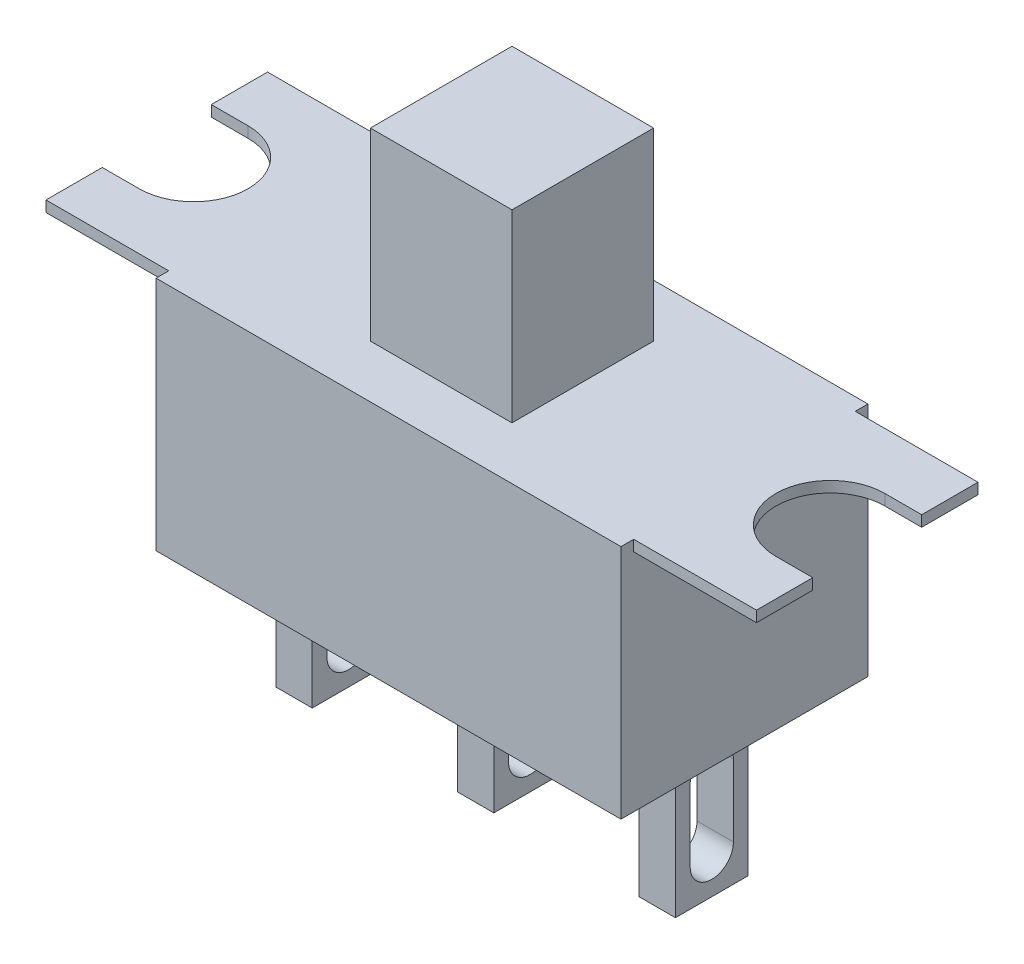
SolidWorks part; units mm, degrees
ref_plane "Front" through (0, 0, 0) normal (0, 0, 1) x (1, 0, 0)
ref_plane "Top" through (0, 0, 0) normal (0, 1, 0) x (1, 0, 0)
ref_plane "Side" through (0, 0, 0) normal (1, 0, 0) x (0, 0, -1)
ref_axis "X_Axis" through (-20.1896, 0, 0) along (1, 0, 0)
ref_axis "Y_Axis" through (0, -14.8261, 0) along (0, 1, 0)
ref_axis "Z_Axis" through (0, 0, -19.842) along (0, 0, 1)
sketch "Sketch1" plane through (0, 0, 0) normal (0, 1, 0) x (1, 0, 0)
  line L1 (6.4, 3.4) -> (-6.4, 3.4)
  line L2 (6.4, 3.4) -> (6.4, -3.4)
  line L3 (6.4, -3.4) -> (-6.4, -3.4)
  line L4 (-6.4, 3.4) -> (-6.4, -3.4)
  line L5 (6.4, 3.4) -> (-6.4, -3.4) construction
  line L6 (6.4, -3.4) -> (-6.4, 3.4) construction
  point P0 (0, 0)
  dimension "D1" = 6.8
  dimension "D2" = 12.8
extrude "Boss-Extrude1" add sketch "Sketch1" along normal blind 6.5
sketch "Sketch2" plane through (0, 6.5, 0) normal (0, 1, 0) x (1, 0, 0)
  line L0 (0, 3.05) -> (0, -3.05) construction
  line L1 (9.78, 3.05) -> (-9.78, 3.05)
  line L2 (9.78, 3.05) -> (9.78, 1.5)
  line L3 (9.78, -3.05) -> (-9.78, -3.05)
  line L4 (-9.78, 3.05) -> (-9.78, 1.5)
  line L5 (9.78, 3.05) -> (-9.78, -3.05) construction
  line L6 (9.78, -3.05) -> (-9.78, 3.05) construction
  line L7 (-8.765, 1.5) -> (-9.78, 1.5)
  line L9 (-9.78, -1.5) -> (-8.765, -1.5)
  line L10 (8.765, 1.5) -> (9.78, 1.5)
  line L12 (9.78, -1.5) -> (8.765, -1.5)
  line L13 (-9.78, -1.5) -> (-9.78, -3.05)
  line L14 (9.78, -1.5) -> (9.78, -3.05)
  arc A0 (-8.765, -1.5) -> (-8.765, 1.5) centre (-8.765, 0) ccw
  arc A1 (8.765, 1.5) -> (8.765, -1.5) centre (8.765, 0) ccw
  point P0 (0, 0)
  dimension "D3" = 3
  dimension "D1" = 6.1
  dimension "D2" = 19.56
  dimension "D4" = 17.53
extrude "Boss-Extrude2" add sketch "Sketch2" against normal blind 0.3
sketch "Sketch3" plane through (0, 6.5, 0) normal (0, 1, 0) x (1, 0, 0)
  line L1 (1.95, 1.95) -> (-1.95, 1.95)
  line L2 (1.95, 1.95) -> (1.95, -1.95)
  line L3 (1.95, -1.95) -> (-1.95, -1.95)
  line L4 (-1.95, 1.95) -> (-1.95, -1.95)
  line L5 (1.95, 1.95) -> (-1.95, -1.95) construction
  line L6 (1.95, -1.95) -> (-1.95, 1.95) construction
  point P0 (0, 0)
  dimension "D1" = 3.9
  dimension "D2" = 3.9
extrude "Boss-Extrude3" add sketch "Sketch3" along normal blind 5.08
sketch "Sketch4" plane through (0, 0, 0) normal (0, -1, 0) x (1, 0, 0)
  line L0 (-6.4, 0) -> (6.4, 0) construction
  line L1 (-0.5, 1) -> (0.5, 1)
  line L2 (-0.5, 1) -> (-0.5, -1)
  line L3 (-0.5, -1) -> (0.5, -1)
  line L4 (0.5, 1) -> (0.5, -1)
  line L5 (-0.5, 1) -> (0.5, -1) construction
  line L6 (-0.5, -1) -> (0.5, 1) construction
  line L7 (4.5, 1) -> (5.5, 1)
  line L8 (4.5, 1) -> (4.5, -1)
  line L9 (4.5, -1) -> (5.5, -1)
  line L10 (5.5, 1) -> (5.5, -1)
  line L11 (4.5, 1) -> (5.5, -1) construction
  line L12 (4.5, -1) -> (5.5, 1) construction
  line L13 (-5.5, 1) -> (-4.5, 1)
  line L14 (-5.5, 1) -> (-5.5, -1)
  line L15 (-5.5, -1) -> (-4.5, -1)
  line L16 (-4.5, 1) -> (-4.5, -1)
  line L17 (-5.5, 1) -> (-4.5, -1) construction
  line L18 (-5.5, -1) -> (-4.5, 1) construction
  line L19 (-6.4, -3.4) -> (-6.4, 3.4) construction
  line L20 (6.4, 3.05) -> (6.4, -3.05) construction
  point P0 (0, 0)
  point P6 (5, 0)
  point P11 (-5, 0)
  dimension "D1" = 2
  dimension "D2" = 1
  dimension "D3" = 4
  dimension "D4" = 4
extrude "Boss-Extrude4" add sketch "Sketch4" along normal blind 4
sketch "Sketch5" plane through (5.5, 0, 0) normal (1, 0, 0) x (0, 0, -1)
  line L0 (0, -1.01) -> (0, -2.99) construction
  line L1 (0.595, -1.01) -> (0.595, -2.99)
  line L2 (-0.595, -1.01) -> (-0.595, -2.99)
  line L3 (-1, -2) -> (1, -2) construction
  line L4 (-1, -4) -> (-1, 0) construction
  line L5 (1, -4) -> (1, 0) construction
  arc A0 (0.595, -1.01) -> (-0.595, -1.01) centre (0, -1.01) ccw
  arc A1 (-0.595, -2.99) -> (0.595, -2.99) centre (0, -2.99) ccw
  point P3 (0, -2)
  dimension "D1" = 1.98
  dimension "D2" = 1.19
extrude "Cut-Extrude1" cut sketch "Sketch5" against normal through all
